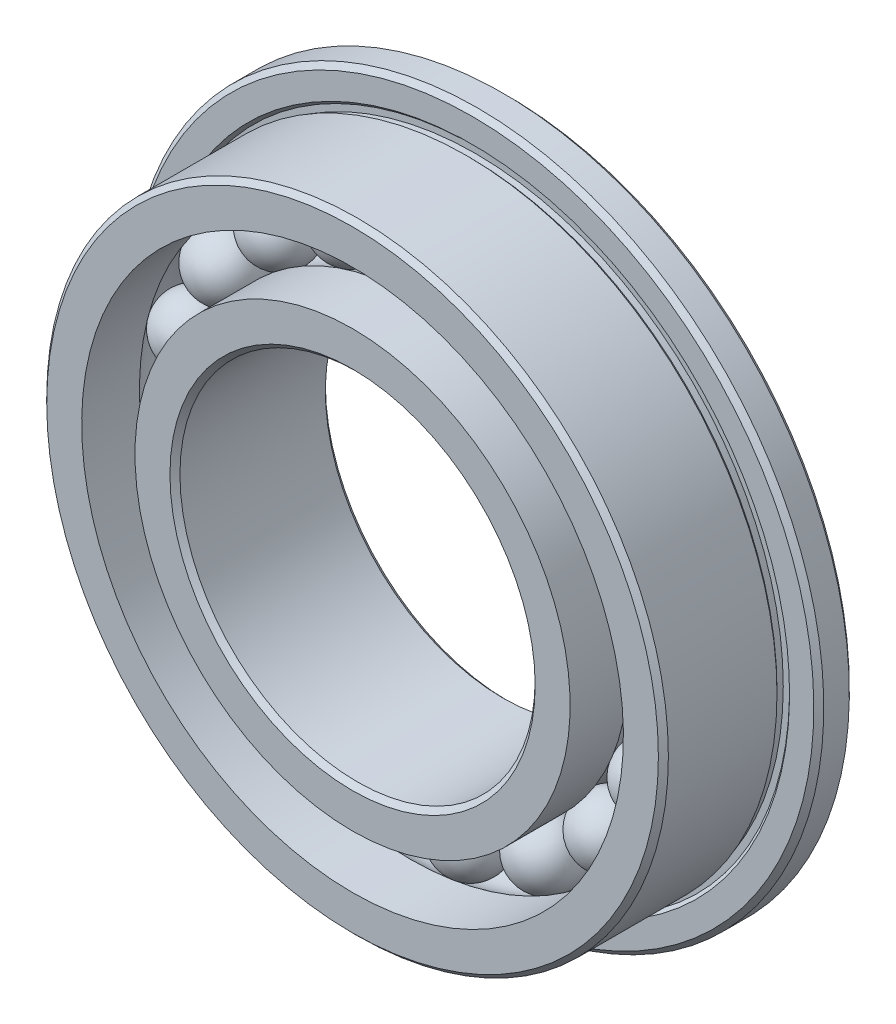
SolidWorks part; units mm, degrees
ref_plane "Front Plane" through (0, 0, 0) normal (0, 0, 1) x (1, 0, 0)
ref_plane "Top Plane" through (0, 0, 0) normal (0, 1, 0) x (1, 0, 0)
ref_plane "Right Plane" through (0, 0, 0) normal (1, 0, 0) x (0, 0, -1)
sketch "Sketch1" plane through (0, 0, 0) normal (1, 0, 0) x (0, 0, -1)
  line L0 (0, 7) -> (0, -7) construction
  line L1 (-1.75, 7) -> (1.75, 7) construction
  line L2 (0, 0) -> (1.75, 0) construction
  line L3 (1.75, 7.8) -> (1.75, -7.8) construction
  line L4 (1.75, -7.8) -> (0.95, -7.8) construction
  line L5 (1.75, 4) -> (0, 4) construction
  line L6 (1.75, 4) -> (1.75, -4) construction
  dimension "OD" = 14
  dimension "Width" = 3.5
  dimension "Flange Thickness" = 0.8
  dimension "ID" = 8
  dimension "Flange OD" = 15.6
sketch "Sketch2" plane through (0, 0, 0) normal (1, 0, 0) x (0, 0, -1)
  line L0 (1.75, 7.8) -> (0.95, 7.8)
  line L1 (0.95, 7.8) -> (0.95, 7.1414)
  line L2 (0.8086, 7) -> (-1.75, 7)
  line L3 (-1.75, 7) -> (-1.75, 6.1)
  line L4 (-1.75, 6.1) -> (-0.45, 6.1)
  line L5 (1.75, 7.8) -> (1.75, -7.8) construction
  line L6 (1.75, 6.1) -> (1.75, 7.8)
  line L7 (1.75, 4) -> (-1.75, 4)
  line L8 (-1.75, 4) -> (-1.75, 4.9)
  line L9 (-1.75, 4.9) -> (-0.45, 4.9)
  line L10 (1.75, 4.9) -> (1.75, 4)
  line L11 (0, 7) -> (0, 4) construction
  line L12 (-0.75, 5.5) -> (0.75, 5.5) construction
  line L13 (0.45, 6.1) -> (1.75, 6.1)
  line L14 (0.45, 4.9) -> (1.75, 4.9)
  line L15 (0.95, 7.1414) -> (1.0207, 7.0707)
  line L16 (1.0207, 7.0707) -> (1.0207, 6.9293)
  line L17 (1.0207, 6.9293) -> (0.8793, 6.9293)
  line L18 (0.8793, 6.9293) -> (0.8086, 7)
  line L19 (0.95, 7) -> (1.0207, 6.9293) construction
  line L20 (1.0207, 7.0707) -> (0.8793, 6.9293) construction
  line L21 (0.8086, 7) -> (0.95, 7) construction
  line L22 (0.95, 7) -> (0.95, 7.1414) construction
  circle A0 centre (0, 5.5) radius 0.75 construction
  arc A1 (-0.45, 6.1) -> (0.45, 6.1) centre (0, 5.5) cw
  arc A2 (-0.45, 4.9) -> (0.45, 4.9) centre (0, 5.5) ccw
  dimension "D1" = 3
  dimension "Ball Dia." = 1.5
  dimension "D2" = 135
  dimension "D3" = 0.2
  dimension "D4" = 1.2
  dimension "Race Thikness" = 0.9
revolve "Revolve1" add sketch "Sketch2" angle 360 about L2
fillet "Fillet1" radius 0.1125 3 edges at (0, -7.8, -1.75) (0, -7.8, -0.95) (0, -7, 1.75) profile chamfer
sketch "Sketch3" plane through (0, 0, 0) normal (0, 0, 1) x (1, 0, 0)
  line L0 (-4, 0) -> (4, 0) construction
  line L1 (-7, 0) -> (7, 0) construction
  point P5 (0, 0)
  dimension "ID2" = 8
  dimension "OD2" = 14
fillet "Fillet2" radius 0.1125 2 edges at (0, -4, -1.75) (0, -4, 1.75) profile chamfer
sketch "Sketch7" plane through (0, 0, 0) normal (0, 0, 1) x (1, 0, 0)
  line L0 (0, 6.25) -> (0, 4.75)
  line L1 (0, 7.8) -> (0, -7.8) construction
  line L2 (-0.8603, 6.25) -> (0, 0) construction
  line L3 (0, 0) -> (0.8603, 6.25) construction
  line L4 (0.8603, 6.25) -> (-0.8603, 6.25) construction
  circle A0 centre (0, 5.5) radius 0.75 construction
  circle A1 centre (0, 0) radius 6.25 construction
  circle A2 centre (0, 0) radius 4.75 construction
  arc A4 (0, 6.25) -> (0, 4.75) centre (0, 5.5) ccw
  dimension "D1" = 15.675
revolve "Revolve3" add sketch "Sketch7" angle 360 about L0
pattern_circular "CirPattern3" count 19 over 360 about axis through (0, 0, 0) along (0, 0, -1) of bodies 107
sketch "Sketch8" plane through (0, 0, 0) normal (1, 0, 0) x (0, 0, -1)
  line L0 (-1.75, 7) -> (1.75, 7) construction
  line L1 (1.75, 7) -> (1.75, 7.8) construction
  line L2 (-1.75, -7) -> (1.75, -7) construction
  line L3 (1.75, 7.8) -> (1.75, -7.8) construction
  dimension "D1" = 14
ref_axis "Axis1" through (0, 0, -1.6375) along (0, 0, 1)
ref_plane "Plane1" through (0, 0, -1.75) normal (0, 0, -1) x (-1, 0, 0)
ref_plane "Plane2" through (0, 0, -0.95) normal (0, 0, 1) x (1, 0, 0)
ref_plane "Plane3" through (0, 0, 1.75) normal (0, 0, 1) x (1, 0, 0)
equation "\"Ball Dia.@Sketch2\" = ( \"OD@Sketch1\" - \"ID@Sketch1\" ) * .25"
equation "\"D3@Sketch2\"=\"Flange Thickness@Sketch1\"/4"
equation "\"D1@Fillet1\" = \"Race Thikness@Sketch2\" / 8"
equation "\"ID2@Sketch3\" = \"ID@Sketch1\""
equation "\"OD2@Sketch3\" = \"OD@Sketch1\""
equation "\"D1@Fillet2\" = \"Race Thikness@Sketch2\" / 8"
equation "\"D1@CirPattern3\"=360/\"D1@Sketch7\"-4"
equation "\"D4@Sketch2\" = ( \"OD@Sketch1\" - \"ID@Sketch1\" ) * .2"
